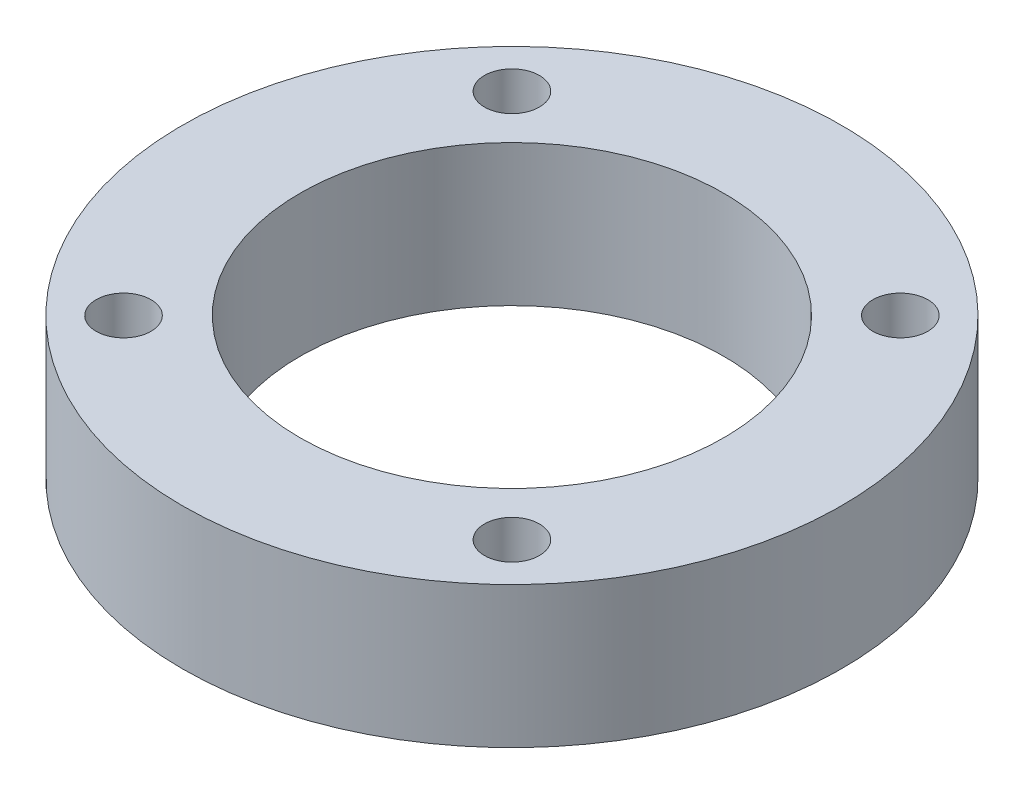
SolidWorks part; units mm, degrees
material "5052-H34"
ref_plane "正面" through (0, 0, 0) normal (0, 0, 1) x (1, 0, 0)
ref_plane "平面" through (0, 0, 0) normal (0, 1, 0) x (1, 0, 0)
ref_plane "右側面" through (0, 0, 0) normal (1, 0, 0) x (0, 0, -1)
sketch "ｽｹｯﾁ1" plane through (0, 0, 0) normal (0, 1, 0) x (1, 0, 0)
  line L0 (0, 0) -> (0, 17.5) construction
  line L1 (0, 0) -> (12.3744, 12.3744) construction
  circle A0 centre (0, 0) radius 13.5
  circle A1 centre (0, 0) radius 17.5 construction
  circle A2 centre (0, 0) radius 21
  circle A3 centre (12.3744, 12.3744) radius 1.75
  circle A4 centre (12.3744, -12.3744) radius 1.75
  circle A5 centre (-12.3744, -12.3744) radius 1.75
  circle A6 centre (-12.3744, 12.3744) radius 1.75
  point P17 (0, 0)
  dimension "D1" = 35
  dimension "D2" = 27
  dimension "D3" = 42
  dimension "D5" = 3.5
  dimension "D4" = 45
  dimension "D6" = 4
extrude "ﾎﾞｽ - 押し出し1" add sketch "ｽｹｯﾁ1" along normal blind 9
